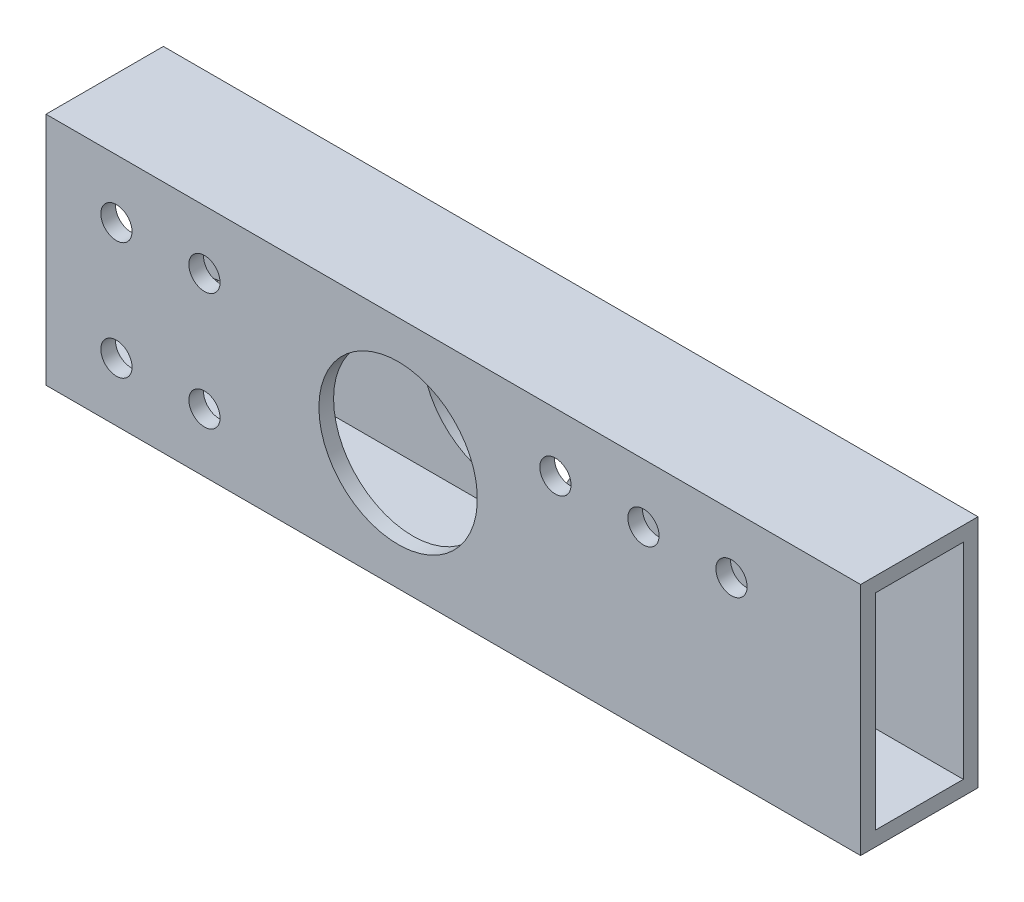
SolidWorks part; units mm, degrees
ref_plane "Front Plane" through (0, 0, 0) normal (0, 0, 1) x (1, 0, 0)
ref_plane "Top Plane" through (0, 0, 0) normal (0, 1, 0) x (1, 0, 0)
ref_plane "Right Plane" through (0, 0, 0) normal (1, 0, 0) x (0, 0, -1)
sketch "Sketch1" plane through (0, 0, 0) normal (0, 1, 0) x (1, 0, 0)
  line L1 (0, 0) -> (176.276, 0)
  line L2 (0, 0) -> (0, 25.4)
  line L3 (0, 25.4) -> (176.276, 25.4)
  line L4 (176.276, 0) -> (176.276, 25.4)
  dimension "D1" = 176.276
  dimension "D2" = 25.4
extrude "Boss-Extrude1" add sketch "Sketch1" along normal blind 50.8
sketch "Sketch2" plane through (176.276, 0, 0) normal (1, 0, 0) x (0, 0, -1)
  line L0 (3.175, 47.625) -> (3.175, 3.175)
  line L1 (0, 50.8) -> (25.4, 50.8)
  line L2 (0, 50.8) -> (0, 0)
  line L3 (0, 0) -> (25.4, 0)
  line L4 (25.4, 50.8) -> (25.4, 0)
  line L5 (3.175, 3.175) -> (22.225, 3.175)
  line L6 (22.225, 47.625) -> (22.225, 3.175)
  line L7 (3.175, 47.625) -> (22.225, 47.625)
  dimension "D1" = 3.175
extrude "Cut-Extrude1" cut sketch "Sketch2" against normal through all flip side to cut
sketch "Sketch3" plane through (0, 0, -25.4) normal (0, 0, -1) x (-1, 0, 0)
  line L1 (-176.276, 50.8) -> (0, 50.8) construction
  line L2 (0, 50.8) -> (0, 0) construction
  circle A0 centre (-76.2, 25.4) radius 17.145
  dimension "D1" = 34.29
  dimension "D4" = 76.2
  dimension "D3" = 25.4
extrude "Cut-Extrude2" cut sketch "Sketch3" against normal through all
sketch "Sketch4" plane through (0, 0, 0) normal (0, 0, 1) x (1, 0, 0)
  line L0 (176.276, 50.8) -> (176.276, 0) construction
  line L2 (0, 50.8) -> (176.276, 50.8) construction
  circle A0 centre (148.336, 38.1) radius 3.3782
  circle A1 centre (129.286, 38.1) radius 3.3782
  circle A2 centre (110.236, 38.1) radius 3.3782
  dimension "D1" = 6.7564
  dimension "D2" = 6.7564
  dimension "D3" = 6.7564
  dimension "D4" = 27.94
  dimension "D5" = 19.05
  dimension "D6" = 19.05
  dimension "D7" = 12.7
  dimension "D8" = 12.7
  dimension "D9" = 12.7
extrude "Cut-Extrude3" cut sketch "Sketch4" against normal through all
sketch "Sketch5" plane through (0, 0, 0) normal (0, 0, 1) x (1, 0, 0)
  line L0 (0, 50.8) -> (0, 0) construction
  line L1 (0, 0) -> (176.276, 0) construction
  line L2 (0, 50.8) -> (176.276, 50.8) construction
  circle A0 centre (15.24, 38.1) radius 3.3782
  circle A1 centre (15.24, 12.7) radius 3.3782
  circle A2 centre (34.29, 12.7) radius 3.3782
  circle A3 centre (34.29, 38.1) radius 3.3782
  dimension "D5" = 6.7564
  dimension "D6" = 6.7564
  dimension "D7" = 6.7564
  dimension "D8" = 6.7564
  dimension "D1" = 15.24
  dimension "D2" = 19.05
  dimension "D3" = 15.24
  dimension "D4" = 19.05
  dimension "D9" = 12.7
  dimension "D10" = 12.7
  dimension "D11" = 12.7
  dimension "D12" = 12.7
extrude "Cut-Extrude4" cut sketch "Sketch5" against normal through all
